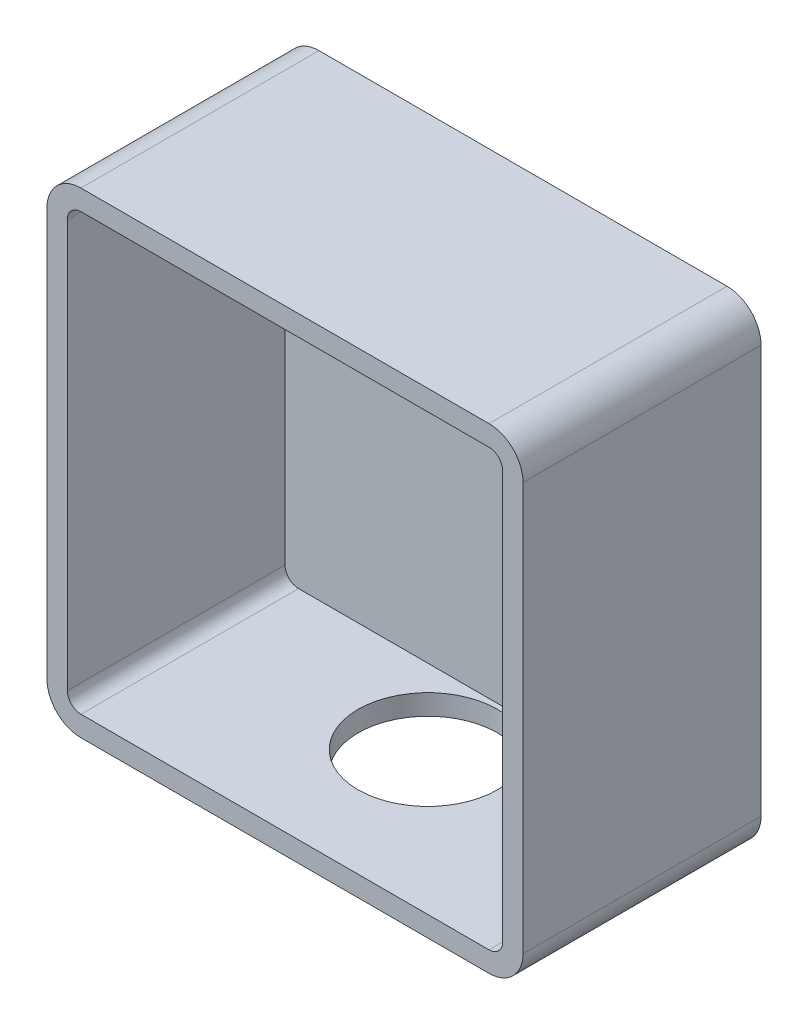
SolidWorks part; units mm, degrees
material "ABS"
ref_plane "Ebene vorne" through (0, 0, 0) normal (0, 0, 1) x (1, 0, 0)
ref_plane "Ebene oben" through (0, 0, 0) normal (0, 1, 0) x (1, 0, 0)
ref_plane "Ebene rechts" through (0, 0, 0) normal (1, 0, 0) x (0, 0, -1)
sketch "Skizze1" plane through (0, 0, 0) normal (0, 0, 1) x (1, 0, 0)
  line L1 (-30, -35) -> (30, -35)
  line L2 (-35, -30) -> (-35, 30)
  line L3 (-30, 35) -> (30, 35)
  line L4 (35, -30) -> (35, 30)
  line L5 (-35, -35) -> (35, 35) construction
  line L6 (-35, 35) -> (35, -35) construction
  arc A0 (-30, -35) -> (-35, -30) centre (-30, -30) cw
  arc A1 (30, -35) -> (35, -30) centre (30, -30) ccw
  arc A2 (30, 35) -> (35, 30) centre (30, 30) cw
  arc A3 (-35, 30) -> (-30, 35) centre (-30, 30) cw
  point P0 (0, 0)
  dimension "D3" = 5
  dimension "D1" = 70
  dimension "D2" = 70
extrude "Aufsatz-Linear austragen1" add sketch "Skizze1" along normal blind 35
shell "Wandung1" thickness 3 removed face at (0, 0, 35)
sketch "Skizze2" plane through (0, -35, 0) normal (0, -1, 0) x (1, 0, 0)
  circle A0 centre (0, 14) radius 10.25
  point P2 (0, 0)
  dimension "D1" = 20.5
  dimension "D2" = 14
extrude "Schnitt-Linear austragen1" cut sketch "Skizze2" against normal up to next
